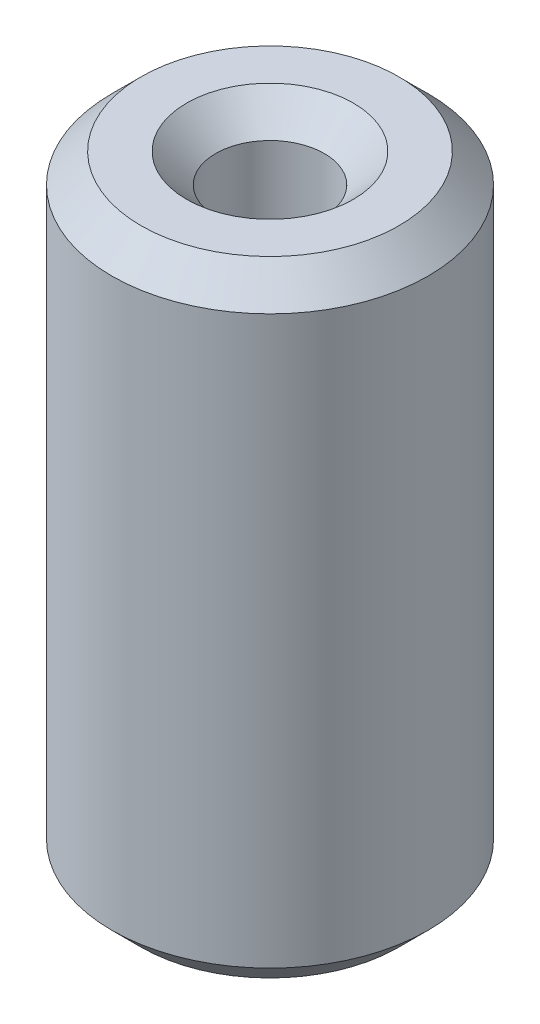
SolidWorks part; units mm, degrees
ref_plane "Front Plane" through (0, 0, 0) normal (0, 0, 1) x (1, 0, 0)
ref_plane "Top Plane" through (0, 0, 0) normal (0, 1, 0) x (1, 0, 0)
ref_plane "Right Plane" through (0, 0, 0) normal (1, 0, 0) x (0, 0, -1)
sketch "Sketch1" plane through (0, 0, 0) normal (0, 1, 0) x (1, 0, 0)
  circle A0 centre (0, 0) radius 7.5
  dimension "SLEEVE_OD" = 15
extrude "Boss-Extrude1" add sketch "Sketch1" along normal blind 29.6455
sketch "Sketch2" plane through (0, 0, 0) normal (0, 1, 0) x (1, 0, 0)
  circle A0 centre (0, 0) radius 2.5772
  dimension "BORE_D" = 5.1544
extrude "Cut-Extrude1" cut sketch "Sketch2" along normal through all
chamfer "Chamfer1" distance 1.3804 angle 45 4 edges at (0, 29.6455, 2.5772) (0, 0, 2.5772) (0, 0, 7.5) (0, 29.6455, 7.5)
